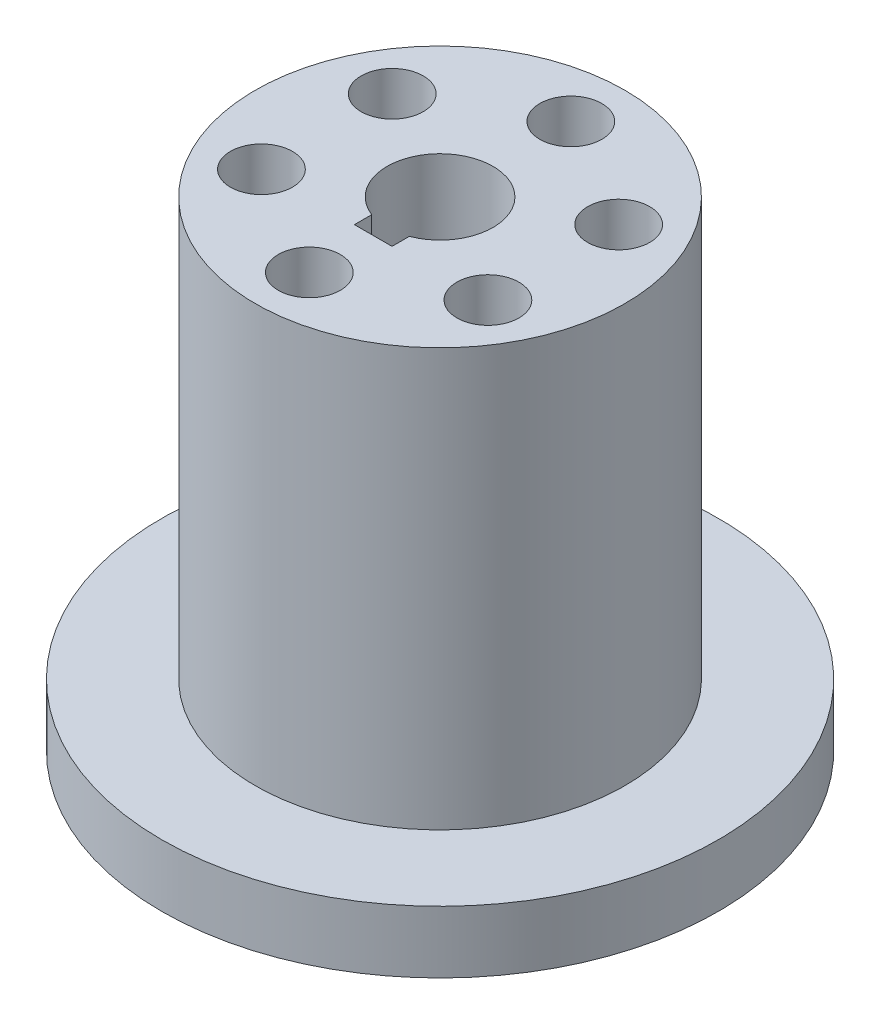
SolidWorks part; units mm, degrees
ref_plane "Front Plane" through (0, 0, 0) normal (0, 0, 1) x (1, 0, 0)
ref_plane "Top Plane" through (0, 0, 0) normal (0, 1, 0) x (1, 0, 0)
ref_plane "Right Plane" through (0, 0, 0) normal (1, 0, 0) x (0, 0, -1)
sketch "Sketch1" plane through (0, 0, 0) normal (0, 1, 0) x (1, 0, 0)
  circle A0 centre (0, 0) radius 38.1
extrude "Boss-Extrude1" add sketch "Sketch1" along normal blind 8.5
sketch "Sketch2" plane through (0, 8.5, 0) normal (0, 1, 0) x (1, 0, 0)
  circle A0 centre (0, 0) radius 25.3
extrude "Boss-Extrude2" add sketch "Sketch2" along normal blind 57.15
sketch "Sketch3" plane through (0, 65.65, 0) normal (0, 1, 0) x (1, 0, 0)
  line L1 (0, 17.8979) -> (-15.5, 8.9489)
  line L2 (-15.5, 8.9489) -> (-15.5, -8.9489)
  line L3 (-15.5, -8.9489) -> (0, -17.8979)
  line L4 (0, -17.8979) -> (15.5, -8.9489)
  line L5 (15.5, -8.9489) -> (15.5, 8.9489)
  line L6 (15.5, 8.9489) -> (0, 17.8979)
  circle A0 centre (0, 0) radius 15.5 construction
  circle A1 centre (0, 17.8979) radius 4.25
  circle A2 centre (15.5, 8.9489) radius 4.25
  circle A3 centre (15.5, -8.9489) radius 4.25
  circle A4 centre (0, -17.8979) radius 4.25
  circle A5 centre (-15.5, -8.9489) radius 4.25
  circle A6 centre (-15.5, 8.9489) radius 4.25
extrude "Cut-Extrude1" cut sketch "Sketch3" against normal blind 78.54 contours L1 A6 L2 | L6 A1 L1 | L5 A2 L6 | L4 A3 L5 | L3 A4 L4 | L2 A5 L3 | L3 A5 L2 | L2 A6 L1 | L1 A1 L6 | L6 A2 L5 | L5 A3 L4 | L4 A4 L3 region at (0, 65.65, -15.5547) region at (0, 65.65, -19.0694) region at (-13.4708, 65.65, -7.7774) region at (-16.5146, 65.65, -9.5347) region at (16.5146, 65.65, -9.5347) region at (13.4708, 65.65, -7.7774) region at (-13.4708, 65.65, 7.7774) region at (-16.5146, 65.65, 9.5347) region at (16.5146, 65.65, 9.5347) region at (13.4708, 65.65, 7.7774) region at (0, 65.65, 15.5547) region at (0, 65.65, 19.0694)
sketch "Sketch4" plane through (0, 0, 0) normal (0, -1, 0) x (1, 0, 0)
  circle A0 centre (-15.5, 8.9489) radius 6.75
  circle A1 centre (0, 17.8979) radius 6.75
  circle A2 centre (15.5, 8.9489) radius 6.75
  circle A3 centre (15.5, -8.9489) radius 6.75
  circle A4 centre (0, -17.8979) radius 6.75
  circle A5 centre (-15.5, -8.9489) radius 6.75
extrude "Cut-Extrude2" cut sketch "Sketch4" against normal blind 8
sketch "Sketch5" plane through (0, 0, 0) normal (0, -1, 0) x (1, 0, 0)
  line L1 (-2.575, 9.15) -> (2.575, 9.15)
  line L2 (-2.575, 9.15) -> (-2.575, 4)
  line L3 (-2.575, 4) -> (2.575, 4)
  line L4 (2.575, 9.15) -> (2.575, 4)
  circle A0 centre (0, 0) radius 7.25
  dimension "D1" = 5.15
  dimension "D2" = 5.15
  dimension "D3" = 9.15
  dimension "D4" = 2.575
extrude "Cut-Extrude3" cut sketch "Sketch5" against normal blind 91 contours L2 A0 L4 L3 | L4 A0 L2 L3 | A0 L4 L1 L2 region at (0, 0, 8.1175) region at (0, 0, 5.5505) region at (0, 0, -0.5929)
